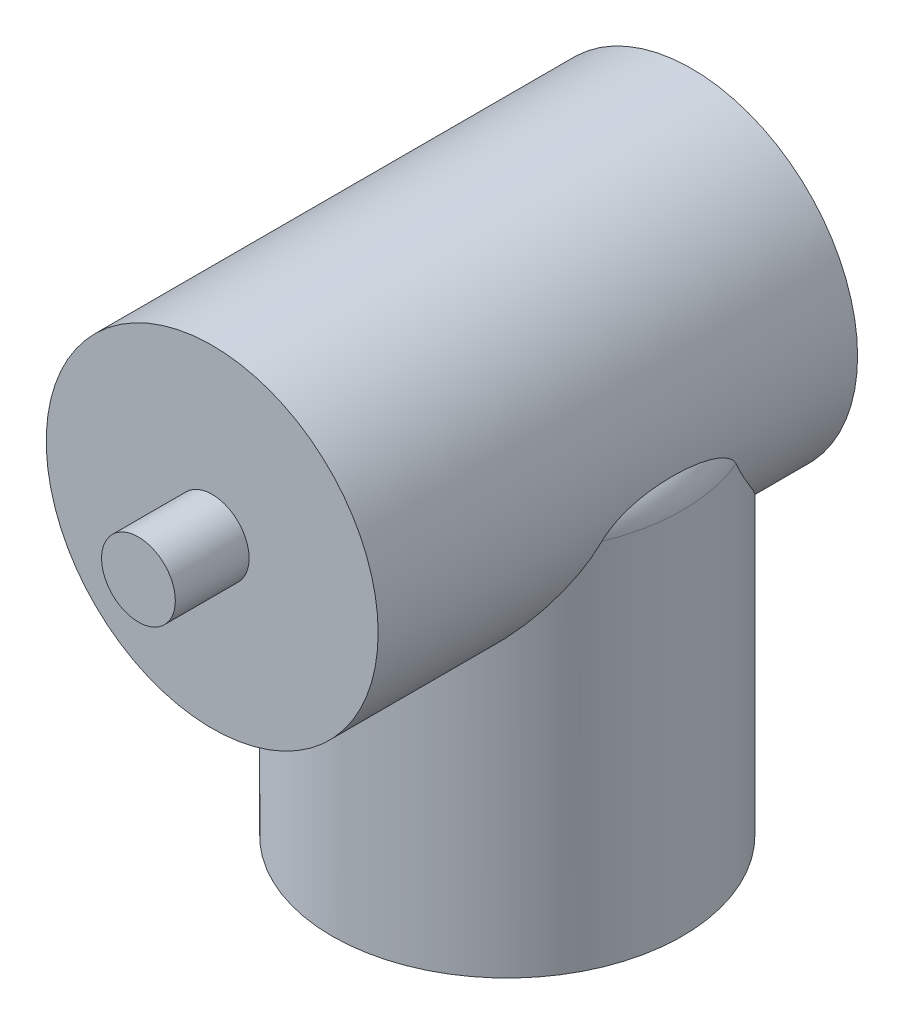
SolidWorks part; units mm, degrees
ref_plane "Front Plane" through (0, 0, 0) normal (0, 0, 1) x (1, 0, 0)
ref_plane "Top Plane" through (0, 0, 0) normal (0, 1, 0) x (1, 0, 0)
ref_plane "Right Plane" through (0, 0, 0) normal (1, 0, 0) x (0, 0, -1)
sketch "Sketch1" plane through (0, 0, 0) normal (0, 0, 1) x (1, 0, 0)
  circle A0 centre (0, 0) radius 45
  dimension "D1" = 90
extrude "Boss-Extrude1" add sketch "Sketch1" along normal blind 130
sketch "Sketch2" plane through (0, 0, 0) normal (0, 1, 0) x (1, 0, 0)
  circle A0 centre (0, -50) radius 47.5
  dimension "D1" = 50
  dimension "D2" = 95
extrude "Boss-Extrude2" add sketch "Sketch2" against normal blind 110
sketch "Sketch4" plane through (0, -110, 0) normal (0, -1, 0) x (1, 0, 0)
  circle A0 centre (0, 50) radius 10
  dimension "D1" = 20
sketch "Sketch5" plane through (0, 0, 130) normal (0, 0, 1) x (1, 0, 0)
  circle A0 centre (0, 0) radius 10
  dimension "D1" = 20
fillet "Fillet1" radius 10 2 edges at (47.5, 0, 50) (-47.5, 0, 50)
ref_plane "Plane1" through (0, 0, 50) normal (0, 0, 1) x (1, 0, 0)
ref_plane "Plane2" through (0, -350, 0) normal (0, -1, 0) x (-1, 0, 0)
extrude "Boss-Extrude3" add sketch "Sketch4" along normal blind 20
extrude "Boss-Extrude4" add sketch "Sketch5" along normal blind 20
sketch "Sketch6" plane through (0, 0, 0) normal (1, 0, 0) x (0, 0, -1)
  line L0 (106.6462, 0) -> (-50, 0) construction
  line L1 (-50, 0) -> (-50, 156.6462) construction
  line L2 (-130, 10) -> (-150, 10) construction
  line L3 (-150, -10) -> (-130, -10) construction
  line L4 (-40, -130) -> (-40, -110) construction
  line L5 (-60, -110) -> (-60, -130) construction
  text T0 "Z1" font "Century Gothic" height 10
  text T1 "Y1" font "Century Gothic" height 10
  point P12 (149.8926, 0)
  point P13 (-48.9523, 0)
  point P14 (-50, 104.2836)
  point P15 (0, 0)
  point P16 (2.2242, -14.3989)
  point P17 (0, 0)
  point P18 (8.6082, -8.9269)
  point P19 (-49.0956, 0)
  point P20 (-50, 156.6462)
sketch "Sketch7" plane through (0, 0, 50) normal (0, 0, 1) x (1, 0, 0)
  line L0 (0, 0) -> (-156.6462, 0) construction
  line L2 (0, 0) -> (0, 156.6462) construction
  text T0 "X1" font "Century Gothic" height 10
  point P3 (-135.649, 0)
  point P6 (162.9123, 0)
